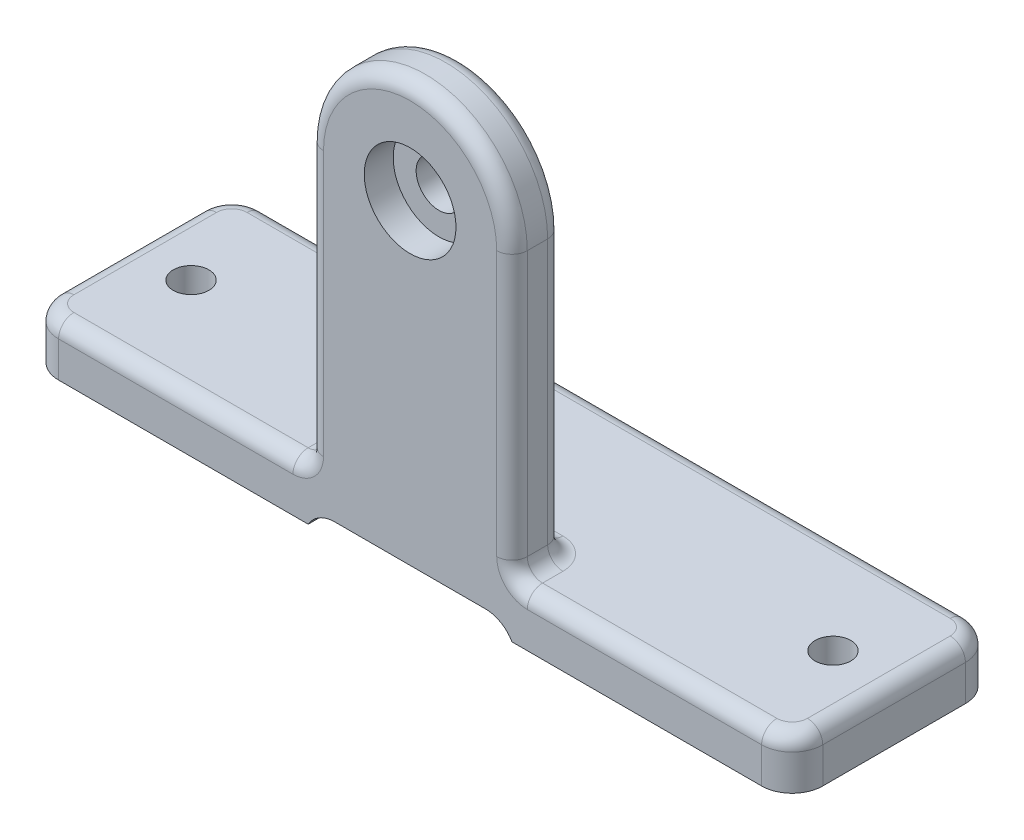
SolidWorks part; units mm, degrees
ref_plane "Front Plane" through (0, 0, 0) normal (0, 0, 1) x (1, 0, 0)
ref_plane "Top Plane" through (0, 0, 0) normal (0, 1, 0) x (1, 0, 0)
ref_plane "Right Plane" through (0, 0, 0) normal (1, 0, 0) x (0, 0, -1)
sketch "Sketch1" plane through (0, 0, 0) normal (0, 1, 0) x (1, 0, 0)
  line L1 (0, 0) -> (150, 0)
  line L2 (0, 0) -> (0, 40)
  line L3 (0, 40) -> (150, 40)
  line L4 (150, 0) -> (150, 40)
  dimension "D1" = 150
  dimension "D2" = 40
extrude "Base Plate" add sketch "Sketch1" along normal blind 10
sketch "Sketch2" plane through (0, 0, 0) normal (0, 0, 1) x (1, 0, 0)
  line L0 (55, 0) -> (55, 65)
  line L1 (0, 0) -> (150, 0) construction
  line L2 (95, 65) -> (95, 0)
  line L3 (95, 0) -> (55, 0)
  line L4 (0, 10) -> (0, 0) construction
  arc A0 (55, 65) -> (95, 65) centre (75, 65) cw
  dimension "D1" = 20
  dimension "D2" = 75
  dimension "D3" = 65
extrude "Vert Boss" add sketch "Sketch2" against normal blind 10
sketch "Sketch5" plane through (0, 0, 0) normal (0, 0, 1) x (1, 0, 0)
  line L0 (0, 0) -> (150, 0) construction
  line L1 (55, 0) -> (95, 0)
  line L2 (55, 0) -> (55, 3)
  line L3 (55, 3) -> (95, 3)
  line L4 (95, 0) -> (95, 3)
  line L5 (55, 65) -> (55, 10) construction
  line L6 (95, 10) -> (95, 65) construction
  dimension "D1" = 3
extrude "Slot" cut sketch "Sketch5" against normal through all
hole_wizard "Ø7.0 (7) 直徑孔1" positions "Sketch9" profile "Sketch8" hole size "Ø7.0" standard "Ansi Metric" end condition through all
sketch "Sketch9" plane through (0, 10, 0) normal (0, 1, 0) x (-1, 0, 0)
  line L0 (-150, 0) -> (-150, -40) construction
  line L1 (-150, -40) -> (0, -40) construction
  line L2 (0, -40) -> (0, 0) construction
  point P0 (-138, -20)
  point P1 (-12, -20)
  dimension "D1" = 12
  dimension "D2" = 20
  dimension "D3" = 12
sketch "Sketch8" plane through (138, 10, -20) normal (1, 0, 0) x (0, 0, 1)
  line L0 (0, 0) -> (0, 10)
  line L1 (0, 10) -> (3.5, 10)
  line L2 (3.5, 10) -> (3.5, 0)
  line L5 (3.5, 0) -> (0, 0)
  line L11 (0, -6.35) -> (0, 107.95) construction
  dimension "Thru Hole Dia." = 7
  dimension "Thru Hole Depth" = 10
hole_wizard "CBORE for M8 Hex Head Bolt1" positions "Sketch4" profile "Sketch3" counterbore size "M8" standard "Ansi Metric" end condition through all
sketch "Sketch4" plane through (0, 0, 0) normal (0, 0, 1) x (1, 0, 0)
  point P0 (75, 65)
sketch "Sketch3" plane through (75, 65, 0) normal (1, 0, 0) x (0, -1, 0)
  line L0 (0, 0) -> (0, 40)
  line L1 (0, 40) -> (4.5, 40)
  line L3 (4.5, 40) -> (4.5, 5.68)
  line L4 (4.5, 5.68) -> (9.005, 5.68)
  line L5 (9.005, 5.68) -> (9.005, 0)
  line L7 (9.005, 0) -> (0, 0)
  line L11 (0, -6.35) -> (0, 107.95) construction
  dimension "Thru Hole Dia." = 9
  dimension "Thru Hole Depth" = 40
  dimension "C'Bore Dia." = 18.01
  dimension "C'Bore Depth" = 5.68
fillet "圓角1" radius 6 6 edges at (95, 3, -20) (55, 3, -20) (0, 5, 0) (0, 5, -40) (150, 5, -40) (150, 5, 0)
fillet "圓角2" radius 3 18 edges at (1.7574, 10, -38.2426) (0, 10, -20) (75, 10, -40) (1.7574, 10, -1.7574) (148.2426, 10, -38.2426) (30.5, 10, 0) (150, 10, -20) (55, 10, -5) (148.2426, 10, -1.7574) (75, 10, -10) (119.5, 10, 0) (95, 37.5, -10) (55, 37.5, -10) (95, 37.5, 0) (55, 37.5, 0) (95, 10, -5) (75, 85, -10) (75, 85, 0)
